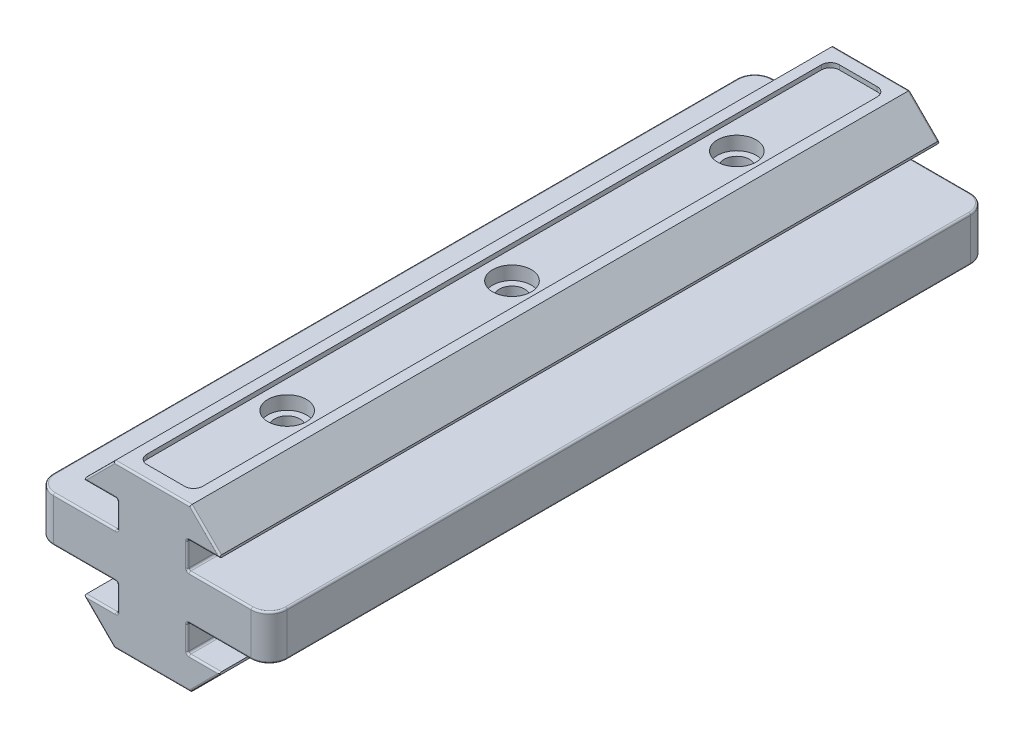
SolidWorks part; units mm, degrees
ref_plane "Front Plane" through (0, 0, 0) normal (0, 0, 1) x (1, 0, 0)
ref_plane "Top Plane" through (0, 0, 0) normal (0, 1, 0) x (1, 0, 0)
ref_plane "Right Plane" through (0, 0, 0) normal (1, 0, 0) x (0, 0, -1)
sketch "Sketch1" plane through (0, 0, 0) normal (0, 0, 1) x (1, 0, 0)
  line L0 (0, 9) -> (0, -9) construction
  line L1 (-13, 0) -> (13, 0) construction
  line L2 (-13, 2.5) -> (-13, -2.5)
  line L3 (13, -2.5) -> (13, 2.5)
  line L4 (13, 2.5) -> (3.8989, 2.5)
  line L5 (3.8989, 2.5) -> (3.8989, 5.5)
  line L7 (-3.8989, 5.5) -> (-3.8989, 2.5)
  line L8 (-3.8989, 2.5) -> (-13, 2.5)
  line L9 (-13, -2.5) -> (-3.8989, -2.5)
  line L10 (-3.8989, -2.5) -> (-3.8989, -5.5)
  line L11 (-3.8989, -5.5) -> (-7.5, -5.5)
  line L12 (-7.5, -5.5) -> (-7.5, -5.754)
  line L13 (-7.5, -5.754) -> (-4.254, -9)
  line L14 (-4.254, -9) -> (4.254, -9)
  line L15 (4.254, -9) -> (7.5, -5.754)
  line L16 (7.5, -5.754) -> (7.5, -5.5)
  line L17 (7.5, -5.5) -> (3.8989, -5.5)
  line L18 (3.8989, -5.5) -> (3.8989, -2.5)
  line L19 (3.8989, -2.5) -> (13, -2.5)
  line L20 (7.5, 5.5) -> (3.8989, 5.5)
  line L21 (7.5, 5.754) -> (7.5, 5.5)
  line L22 (4.254, 9) -> (7.5, 5.754)
  line L23 (-4.254, 9) -> (4.254, 9)
  line L24 (-7.5, 5.754) -> (-4.254, 9)
  line L25 (-7.5, 5.5) -> (-7.5, 5.754)
  line L26 (-3.8989, 5.5) -> (-7.5, 5.5)
  dimension "D1" = 5
  dimension "A" = 18
  dimension "N" = 7.7978
  dimension "D2" = 0.254
  dimension "Width" = 26
  dimension "D" = 15
  dimension "C" = 3
  dimension "D3" = 45
sketch "Sketch2" plane through (0, 0, 0) normal (0, 1, 0) x (1, 0, 0)
  line L0 (0, 40) -> (0, -40)
  line L2 (-4.254, 0) -> (4.254, 0) construction
  line L4 (-3.0988, 38.5) -> (3.0988, 38.5)
  line L5 (-3.0988, 38.5) -> (-3.0988, -38.5)
  line L6 (-3.0988, -38.5) -> (3.0988, -38.5)
  line L7 (3.0988, 38.5) -> (3.0988, -38.5)
  line L8 (-3.0988, 38.5) -> (3.0988, -38.5) construction
  line L9 (-3.0988, -38.5) -> (3.0988, 38.5) construction
  circle A0 centre (0, -25) radius 1.4
  circle A1 centre (0, 25) radius 1.4
  circle A3 centre (0, 0) radius 1.4
  circle A4 centre (0, -25) radius 2.15
  circle A5 centre (0, 0) radius 2.15
  circle A6 centre (0, 25) radius 2.15
  point P3 (0, 0)
  dimension "D2" = 15
  dimension "D4" = 4.3
  dimension "E" = 2.8
  dimension "Length" = 80
  dimension "D3" = 25
  dimension "D5" = 77
  dimension "D6" = 6.1976
sketch "Sketch3" plane through (0, 0, 0) normal (0, 0, 1) x (1, 0, 0)
  line L18 (-13, 2.5) -> (-13, -2.5)
  line L19 (-3.8989, 2.5) -> (-13, 2.5)
  line L20 (-3.8989, 5.5) -> (-3.8989, 2.5)
  line L21 (3.8989, 5.5) -> (7.5, 5.5)
  line L22 (3.8989, 2.5) -> (3.8989, 5.5)
  line L23 (13, 2.5) -> (3.8989, 2.5)
  line L24 (13, -2.5) -> (13, 2.5)
  line L25 (3.8989, -2.5) -> (13, -2.5)
  line L26 (3.8989, -5.5) -> (3.8989, -2.5)
  line L27 (7.5, -5.5) -> (3.8989, -5.5)
  line L28 (7.5, -5.754) -> (7.5, -5.5)
  line L29 (4.254, -9) -> (7.5, -5.754)
  line L30 (-4.254, -9) -> (4.254, -9)
  line L31 (-7.5, -5.754) -> (-4.254, -9)
  line L32 (-7.5, -5.5) -> (-7.5, -5.754)
  line L33 (-3.8989, -5.5) -> (-7.5, -5.5)
  line L34 (-3.8989, -2.5) -> (-3.8989, -5.5)
  line L35 (-13, -2.5) -> (-3.8989, -2.5)
  line L36 (-13, 2.5) -> (-13, -2.5)
  line L37 (-3.8989, 2.5) -> (-13, 2.5)
  line L38 (-3.8989, 5.5) -> (-3.8989, 2.5)
  line L40 (3.8989, 2.5) -> (3.8989, 5.5)
  line L41 (13, 2.5) -> (3.8989, 2.5)
  line L42 (13, -2.5) -> (13, 2.5)
  line L43 (3.8989, -2.5) -> (13, -2.5)
  line L44 (3.8989, -5.5) -> (3.8989, -2.5)
  line L45 (7.5, -5.5) -> (3.8989, -5.5)
  line L46 (7.5, -5.754) -> (7.5, -5.5)
  line L47 (4.254, -9) -> (7.5, -5.754)
  line L48 (-4.254, -9) -> (4.254, -9)
  line L49 (-7.5, -5.754) -> (-4.254, -9)
  line L50 (-7.5, -5.5) -> (-7.5, -5.754)
  line L51 (-3.8989, -5.5) -> (-7.5, -5.5)
  line L52 (-3.8989, -2.5) -> (-3.8989, -5.5)
  line L53 (-13, -2.5) -> (-3.8989, -2.5)
  line L60 (3.8989, 5.5) -> (7.5, 5.5)
  line L61 (7.5, 5.5) -> (7.5, 5.754)
  line L62 (7.5, 5.5) -> (7.5, 5.754)
  line L63 (7.5, 5.754) -> (4.254, 9)
  line L64 (7.5, 5.754) -> (4.254, 9)
  line L65 (4.254, 9) -> (-4.254, 9)
  line L66 (4.254, 9) -> (-4.254, 9)
  line L67 (-4.254, 9) -> (-7.5, 5.754)
  line L68 (-4.254, 9) -> (-7.5, 5.754)
  line L69 (-7.5, 5.754) -> (-7.5, 5.5)
  line L70 (-7.5, 5.754) -> (-7.5, 5.5)
  line L71 (-7.5, 5.5) -> (-3.8989, 5.5)
  line L72 (-7.5, 5.5) -> (-3.8989, 5.5)
  dimension "D1" = 0
extrude "Boss-Extrude1" add sketch "Sketch3" against normal up to vertex (40 mm away) and the other way up to vertex (40 mm away) up to point (0, 0, -40) other way up to point (0, 0, 40)
sketch "Sketch4" plane through (0, 0, 0) normal (0, 1, 0) x (1, 0, 0)
  circle A0 centre (0, 25) radius 1.4 construction
  circle A1 centre (0, 0) radius 1.4 construction
  circle A2 centre (0, -25) radius 1.4 construction
  circle A3 centre (0, 25) radius 1.4
  circle A4 centre (0, 0) radius 1.4
  circle A5 centre (0, -25) radius 1.4
extrude "Cut-Extrude1" cut sketch "Sketch4" against normal through all both and the other way through all
sketch "Sketch5" plane through (0, 9, 0) normal (0, 1, 0) x (1, 0, 0)
  circle A0 centre (0, 0) radius 2.15 construction
  circle A1 centre (0, 25) radius 2.15 construction
  circle A2 centre (0, -25) radius 2.15 construction
  circle A3 centre (0, 0) radius 2.15
  circle A4 centre (0, 25) radius 2.15
  circle A5 centre (0, -25) radius 2.15
extrude "Cut-Extrude2" cut sketch "Sketch5" against normal blind 2
sketch "Sketch6" plane through (0, 9, 0) normal (0, 1, 0) x (1, 0, 0)
  line L0 (-3.0988, 38.5) -> (3.0988, 38.5) construction
  line L1 (-3.0988, 38.5) -> (-3.0988, -38.5) construction
  line L2 (3.0988, 38.5) -> (3.0988, -38.5) construction
  line L3 (-3.0988, -38.5) -> (3.0988, -38.5) construction
  line L4 (-2.0988, 38.5) -> (2.0988, 38.5)
  line L5 (-3.0988, 37.5) -> (-3.0988, -37.5)
  line L6 (3.0988, 37.5) -> (3.0988, -37.5)
  line L7 (-2.0988, -38.5) -> (2.0988, -38.5)
  arc A0 (-2.0988, 38.5) -> (-3.0988, 37.5) centre (-2.0988, 37.5) ccw
  arc A1 (2.0988, 38.5) -> (3.0988, 37.5) centre (2.0988, 37.5) cw
  arc A2 (-3.0988, -37.5) -> (-2.0988, -38.5) centre (-2.0988, -37.5) ccw
  arc A3 (3.0988, -37.5) -> (2.0988, -38.5) centre (2.0988, -37.5) cw
  dimension "D1" = 1
extrude "Cut-Extrude3" cut sketch "Sketch6" against normal blind 0.5
mirror "Mirror1" about plane through (0, 0, 0) normal (0, 1, 0) of "Cut-Extrude3", "Cut-Extrude2"
fillet "Fillet1" radius 2.0066 4 edges at (-13, 0, -40) (13, 0, -40) (-13, 0, 40) (13, 0, 40)
fillet "Fillet4" radius 0.2 56 edges at (12.4123, -2.5, 39.4123) (13, -2.5, 0) (12.4123, -2.5, -39.4123) (12.4123, 2.5, 39.4123) (13, 2.5, 0) (12.4123, 2.5, -39.4123) (-12.4123, 2.5, 39.4123) (-13, 2.5, 0) (-12.4123, 2.5, -39.4123) (-12.4123, -2.5, 39.4123) (-13, -2.5, 0) (-12.4123, -2.5, -39.4123) (3.8989, -5.5, 0) (3.8989, -2.5, 0) (3.8989, 2.5, 0) (3.8989, 5.5, 0) (-3.8989, -2.5, 0) (-3.8989, -5.5, 0) (-3.8989, 5.5, 0) (-3.8989, 2.5, 0) (-3.8989, 4, 40) (-5.6994, 5.5, 40) (-5.877, 7.377, 40) (0, 9, 40) (5.877, 7.377, 40) (5.6995, 5.5, 40) (3.8989, 4, 40) (7.4462, 2.5, 40) (7.4462, -2.5, 40) (3.8989, -4, 40) (5.6995, -5.5, 40) (5.877, -7.377, 40) (0, -9, 40) (-5.877, -7.377, 40) (-5.6994, -5.5, 40) (-3.8989, -4, 40) (-7.4462, -2.5, 40) (-7.4462, 2.5, 40) (-3.8989, -4, -40) (-5.6994, -5.5, -40) (-5.877, -7.377, -40) (0, -9, -40) (5.877, -7.377, -40) (5.6995, -5.5, -40) (3.8989, -4, -40) (7.4462, -2.5, -40) (7.4462, 2.5, -40) (3.8989, 4, -40) (5.6995, 5.5, -40) (5.877, 7.377, -40) (0, 9, -40) (-5.877, 7.377, -40) (-5.6994, 5.5, -40) (-3.8989, 4, -40) (-7.4462, 2.5, -40) (-7.4462, -2.5, -40)
